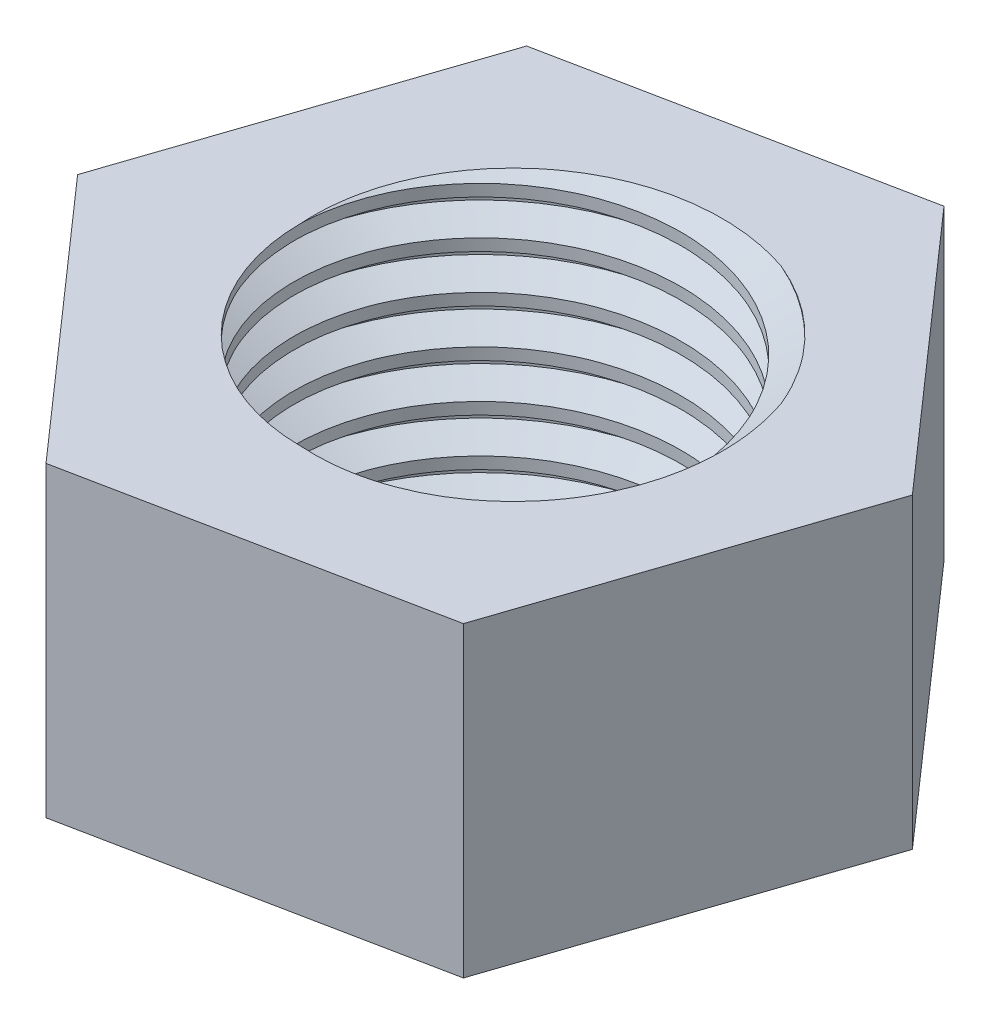
SolidWorks part; units mm, degrees
ref_plane "Płaszczyzna przednia" through (0, 0, 0) normal (0, 0, 1) x (1, 0, 0)
ref_plane "Płaszczyzna górna" through (0, 0, 0) normal (0, 1, 0) x (1, 0, 0)
ref_plane "Płaszczyzna prawa" through (0, 0, 0) normal (1, 0, 0) x (0, 0, -1)
sketch "Szkic1" plane through (0, 0, 0) normal (0, 1, 0) x (1, 0, 0)
  line L1 (7.3579, 1.4815) -> (2.396, 7.1129)
  line L2 (2.396, 7.1129) -> (-4.9619, 5.6314)
  line L3 (-4.9619, 5.6314) -> (-7.3579, -1.4815)
  line L4 (-7.3579, -1.4815) -> (-2.396, -7.1129)
  line L5 (-2.396, -7.1129) -> (4.9619, -5.6314)
  line L6 (4.9619, -5.6314) -> (7.3579, 1.4815)
  circle A0 centre (0, 0) radius 6.5 construction
  circle A1 centre (0, 0) radius 4.1
  dimension "d" = 8.2
  dimension "s" = 13
extrude "Dodanie-wyciągnięcie1" add sketch "Szkic1" along normal blind 6.5
thread "Gwint1" [suppressed] pitch 0.7 start angle 0, offset 1, length 0, pitch 0.7, diameter 4
ref_plane "Płaszczyzna1" through (-2, 4.2, 0) normal (0, 0, 1) x (-1, 0, 0)
sketch "Profil gwintu1" plane through (-2, 4.2, 0) normal (0, 0, 1) x (-1, 0, 0)
  line L0 (0, 0) -> (0, 0.7) construction
  line L1 (0, 0) -> (0.3789, 0.2187)
  line L2 (0.3789, 0.2187) -> (0.3789, 0.3062)
  line L3 (0.3789, 0.3062) -> (0, 0.525)
  line L4 (0.3789, 0.2625) -> (0, 0.2625) construction
  line L11 (0, 0) -> (0, 0.525)
  point P2 (0, 0)
  dimension "Pitch" = 0.7
  dimension "Profile_Angle" = 60
  dimension "Profile_Land" = 0.0875
  dimension "Profile_Height" = 0.3789
thread "Gwint2" [suppressed] pitch 0.5 start angle 0, offset 1, length 0, pitch 0.5, diameter 3.2
ref_plane "Płaszczyzna2" through (1.6, -1, 0) normal (0, 0, 1) x (1, 0, 0)
sketch "Profil gwintu2" plane through (1.6, -1, 0) normal (0, 0, 1) x (1, 0, 0)
  line L0 (0, 0) -> (0, 0.5) construction
  line L1 (0, 0) -> (0.2706, 0.1562)
  line L2 (0.2706, 0.1562) -> (0.2706, 0.2187)
  line L3 (0.2706, 0.2187) -> (0, 0.375)
  line L4 (0.2706, 0.1875) -> (0, 0.1875) construction
  line L11 (0, 0) -> (0, 0.375)
  point P2 (0, 0)
  dimension "Pitch" = 0.5
  dimension "Profile_Angle" = 60
  dimension "Profile_Land" = 0.0625
  dimension "Profile_Height" = 0.2706
thread "Gwint3" pitch 1 method cut profile "Profil gwintu3" start angle 0, offset 1, length 0, pitch 1, diameter 8.2
ref_plane "Płaszczyzna3" through (4.1, -1, 0) normal (0, 0, 1) x (1, 0, 0)
sketch "Profil gwintu3" plane through (4.1, -1, 0) normal (0, 0, 1) x (1, 0, 0)
  line L0 (0, 0) -> (0, 1) construction
  line L1 (0, 0) -> (0.5413, 0.3125)
  line L2 (0.5413, 0.3125) -> (0.5413, 0.4375)
  line L3 (0.5413, 0.4375) -> (0, 0.75)
  line L4 (0.5413, 0.375) -> (0, 0.375) construction
  line L11 (0, 0) -> (0, 0.75)
  point P2 (0, 0)
  dimension "Pitch" = 1
  dimension "Profile_Angle" = 60
  dimension "Profile_Land" = 0.125
  dimension "Profile_Height" = 0.5413
